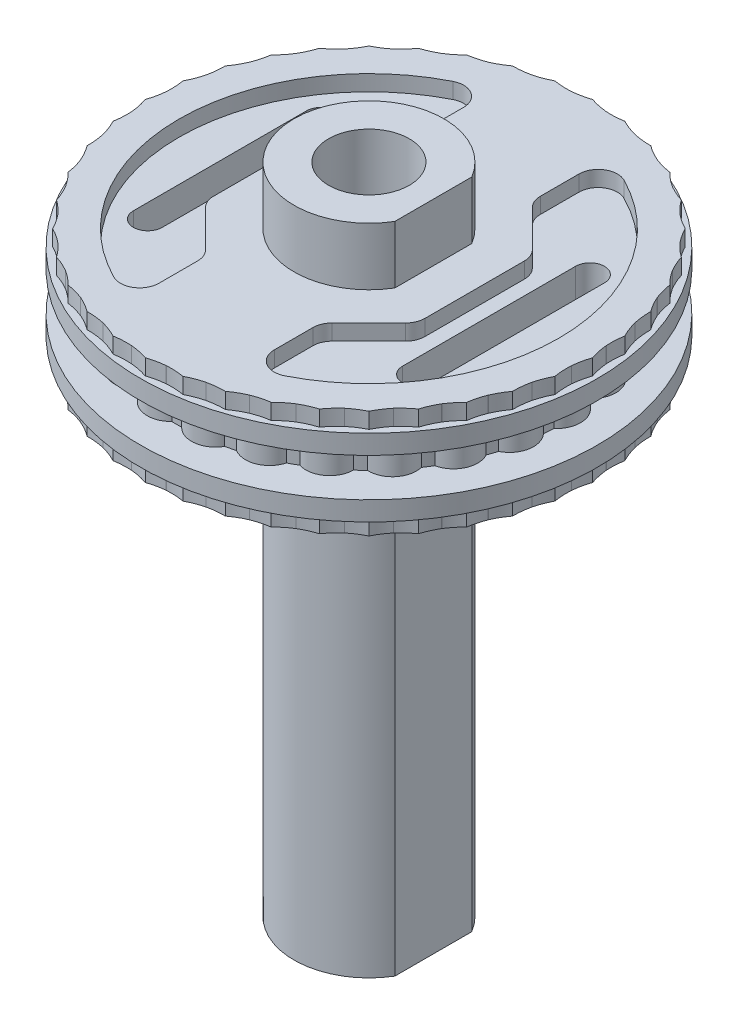
SolidWorks part; units mm, degrees
ref_plane "Front Plane" through (0, 0, 0) normal (0, 0, 1) x (1, 0, 0)
ref_plane "Top Plane" through (0, 0, 0) normal (0, 1, 0) x (1, 0, 0)
ref_plane "Right Plane" through (0, 0, 0) normal (1, 0, 0) x (0, 0, -1)
sketch "Sketch1" plane through (0, 0, 0) normal (1, 0, 0) x (0, 0, -1)
  line L0 (0, -0.599) -> (0, 0.599) construction
  line L1 (-5, -0.5) -> (0, -0.5)
  line L2 (-5, -0.5) -> (-5, 0.5)
  line L3 (-5, 0.5) -> (0, 0.5)
  line L4 (0, -0.5) -> (0, 0.5)
  line L5 (-5, -0.5) -> (0, 0.5) construction
  line L6 (-5, 0.5) -> (0, -0.5) construction
  point P0 (-2.5, 0)
  point P8 (0, 0)
  dimension "D2" = 5
  dimension "D3" = 1
revolve "Revolve1" add sketch "Sketch1" angle 360 about L0
sketch "Sketch2" plane through (0, 0.5, 0) normal (0, 1, 0) x (1, 0, 0)
  line L0 (0, 0) -> (0, 5.2249) construction
  arc A0 (-0.5, 4.9749) -> (0.5, 4.9749) centre (0, 4.5999) cw
  circle A1 centre (0, 0) radius 5 construction
  circle A4 centre (0, 0) radius 5
  arc A5 (0.5, 4.9749) -> (-0.5, 4.9749) centre (0, 0) ccw
  dimension "D1" = 0
  dimension "D2" = 1
  dimension "D3" = 0.25
extrude "Boss-Extrude1" add sketch "Sketch2" against normal up to surface (1 mm away) from surface up to face at (0, -0.5, -5) starting at face at (0, 0.5, -5)
pattern_circular "CirPattern1" count 25 over 360 about axis through (0, 0.5, 0) along (0, -1, 0) of "Boss-Extrude1"
sketch "Sketch3" plane through (0, 0, 0) normal (1, 0, 0) x (0, 0, -1)
  line L0 (0, 0) -> (0, 0.5) construction
  line L1 (0, 0.5) -> (-5.9387, 0.5)
  line L3 (-5.7387, 1) -> (-5.9387, 1)
  line L4 (-5.9387, 0.5) -> (-5.9387, 1)
  line L6 (0, 0.5) -> (0, 1.4)
  line L7 (0, 1.4) -> (-5.7387, 1.4)
  line L8 (-5.7387, 1) -> (-5.7387, 1.4)
  line L9 (0.8114, 0.5) -> (-0.1866, 0.5) construction
  line L10 (-5.1887, 0.5) -> (-5.1887, -0.5) construction
  dimension "D1" = 0.5
  dimension "D2" = 0.4
  dimension "D3" = 0.75
  dimension "D4" = 0.2
revolve "Revolve2" add sketch "Sketch3" angle 360 about L0
sketch "Sketch4" plane through (0, 1.4, 0) normal (0, 1, 0) x (1, 0, 0)
  line L0 (0, 0) -> (0, 5.8168) construction
  arc A0 (-0.5, 5.7168) -> (0, 5.8168) centre (-0.639, 7.712) ccw
  arc A1 (0, 5.8168) -> (0.5, 5.7168) centre (0.639, 7.712) ccw
  circle A3 centre (0, 0) radius 5.7387 construction
  circle A4 centre (0, 0) radius 5.7387
  arc A5 (0.5, 5.7168) -> (-0.5, 5.7168) centre (0, 0) ccw
  circle M2 centre (0, 0) radius 5.7387
  dimension "D4" = 2
  dimension "D2" = 0.1
  dimension "D3" = 1
  dimension "D1" = 0
extrude "Boss-Extrude2" add sketch "Sketch4" against normal up to surface (0.4 mm away) contours L0 A1 M2 | A5 L0 A0 region at (-0.117, 1.4, -5.7602) region at (0.117, 1.4, -5.7602) up to face at (0, 1, -5.9387)
pattern_circular "CirPattern2" count 40 over 360 about axis through (0, 1.4, 0) along (0, -1, 0) of "Boss-Extrude2"
mirror "Mirror2" about plane through (0, 0, 0) normal (0, 1, 0) of "Revolve2", "Boss-Extrude2", "CirPattern2"
sketch "Sketch16" plane through (0, 1.4, 0) normal (0, 1, 0) x (1, 0, 0)
  line L80 (-1.3373, 5.5807) -> (-1.3421, 5.5795)
  line L81 (-2.1938, 5.3028) -> (-2.1984, 5.3009)
  line L82 (-2.9963, 4.8943) -> (-3.0006, 4.8917)
  line L83 (-3.7251, 4.3653) -> (-3.7289, 4.3621)
  line L84 (-4.3621, 3.7289) -> (-4.3653, 3.7251)
  line L85 (-4.8917, 3.0006) -> (-4.8943, 2.9963)
  line L86 (-5.3009, 2.1984) -> (-5.3028, 2.1938)
  line L87 (-5.5795, 1.3421) -> (-5.5807, 1.3373)
  line L88 (-5.7208, 0.4527) -> (-5.7212, 0.4478)
  line L89 (-5.7212, -0.4478) -> (-5.7208, -0.4527)
  line L90 (-5.5807, -1.3373) -> (-5.5795, -1.3421)
  line L91 (-5.3028, -2.1938) -> (-5.3009, -2.1984)
  line L92 (-4.8943, -2.9963) -> (-4.8917, -3.0006)
  line L93 (-4.3653, -3.7251) -> (-4.3621, -3.7289)
  line L94 (-3.7289, -4.3621) -> (-3.7251, -4.3653)
  line L95 (-3.0006, -4.8917) -> (-2.9963, -4.8943)
  line L96 (-2.1984, -5.3009) -> (-2.1938, -5.3028)
  line L97 (-1.3421, -5.5795) -> (-1.3373, -5.5807)
  line L98 (-0.4527, -5.7208) -> (-0.4478, -5.7212)
  line L99 (0.4478, -5.7212) -> (0.4527, -5.7208)
  line L100 (1.3373, -5.5807) -> (1.3421, -5.5795)
  line L101 (2.1938, -5.3028) -> (2.1984, -5.3009)
  line L102 (2.9963, -4.8943) -> (3.0006, -4.8917)
  line L103 (3.7251, -4.3653) -> (3.7289, -4.3621)
  line L104 (4.3621, -3.7289) -> (4.3653, -3.7251)
  line L105 (4.8917, -3.0006) -> (4.8943, -2.9963)
  line L106 (5.3009, -2.1984) -> (5.3028, -2.1938)
  line L107 (5.5795, -1.3421) -> (5.5807, -1.3373)
  line L108 (5.7208, -0.4527) -> (5.7212, -0.4478)
  line L109 (5.7212, 0.4478) -> (5.7208, 0.4527)
  line L110 (5.5807, 1.3373) -> (5.5795, 1.3421)
  line L111 (5.3028, 2.1938) -> (5.3009, 2.1984)
  line L112 (4.8943, 2.9963) -> (4.8917, 3.0006)
  line L113 (4.3653, 3.7251) -> (4.3621, 3.7289)
  line L114 (3.7289, 4.3621) -> (3.7251, 4.3653)
  line L115 (3.0006, 4.8917) -> (2.9963, 4.8943)
  line L116 (2.1984, 5.3009) -> (2.1938, 5.3028)
  line L117 (1.3421, 5.5795) -> (1.3373, 5.5807)
  line L118 (0.4527, 5.7208) -> (0.4478, 5.7212)
  line L119 (-0.4478, 5.7212) -> (-0.4527, 5.7208)
  line L120 (-1.3373, 5.5807) -> (-1.3421, 5.5795)
  line L121 (-2.1938, 5.3028) -> (-2.1984, 5.3009)
  line L122 (-2.9963, 4.8943) -> (-3.0006, 4.8917)
  line L123 (-3.7251, 4.3653) -> (-3.7289, 4.3621)
  line L124 (-4.3621, 3.7289) -> (-4.3653, 3.7251)
  line L125 (-4.8917, 3.0006) -> (-4.8943, 2.9963)
  line L126 (-5.3009, 2.1984) -> (-5.3028, 2.1938)
  line L127 (-5.5795, 1.3421) -> (-5.5807, 1.3373)
  line L128 (-5.7208, 0.4527) -> (-5.7212, 0.4478)
  line L129 (-5.7212, -0.4478) -> (-5.7208, -0.4527)
  line L130 (-5.5807, -1.3373) -> (-5.5795, -1.3421)
  line L131 (-5.3028, -2.1938) -> (-5.3009, -2.1984)
  line L132 (-4.8943, -2.9963) -> (-4.8917, -3.0006)
  line L133 (-4.3653, -3.7251) -> (-4.3621, -3.7289)
  line L134 (-3.7289, -4.3621) -> (-3.7251, -4.3653)
  line L135 (-3.0006, -4.8917) -> (-2.9963, -4.8943)
  line L136 (-2.1984, -5.3009) -> (-2.1938, -5.3028)
  line L137 (-1.3421, -5.5795) -> (-1.3373, -5.5807)
  line L138 (-0.4527, -5.7208) -> (-0.4478, -5.7212)
  line L139 (0.4478, -5.7212) -> (0.4527, -5.7208)
  line L140 (1.3373, -5.5807) -> (1.3421, -5.5795)
  line L141 (2.1938, -5.3028) -> (2.1984, -5.3009)
  line L142 (2.9963, -4.8943) -> (3.0006, -4.8917)
  line L143 (3.7251, -4.3653) -> (3.7289, -4.3621)
  line L144 (4.3621, -3.7289) -> (4.3653, -3.7251)
  line L145 (4.8917, -3.0006) -> (4.8943, -2.9963)
  line L146 (5.3009, -2.1984) -> (5.3028, -2.1938)
  line L147 (5.5795, -1.3421) -> (5.5807, -1.3373)
  line L148 (5.7208, -0.4527) -> (5.7212, -0.4478)
  line L149 (5.7212, 0.4478) -> (5.7208, 0.4527)
  line L150 (5.5807, 1.3373) -> (5.5795, 1.3421)
  line L151 (5.3028, 2.1938) -> (5.3009, 2.1984)
  line L152 (4.8943, 2.9963) -> (4.8917, 3.0006)
  line L153 (4.3653, 3.7251) -> (4.3621, 3.7289)
  line L154 (3.7289, 4.3621) -> (3.7251, 4.3653)
  line L155 (3.0006, 4.8917) -> (2.9963, 4.8943)
  line L156 (2.1984, 5.3009) -> (2.1938, 5.3028)
  line L157 (1.3421, 5.5795) -> (1.3373, 5.5807)
  line L158 (0.4527, 5.7208) -> (0.4478, 5.7212)
  line L159 (-0.4478, 5.7212) -> (-0.4527, 5.7208)
  arc A160 (-1.7975, 5.5321) -> (-1.3421, 5.5795) centre (-1.7754, 7.532) ccw
  arc A161 (-2.1938, 5.3028) -> (-1.7975, 5.5321) centre (-2.9909, 7.1371) ccw
  arc A162 (-2.6408, 5.1828) -> (-2.1984, 5.3009) centre (-2.9318, 7.1616) ccw
  arc A163 (-2.9963, 4.8943) -> (-2.6408, 5.1828) centre (-4.0706, 6.5813) ccw
  arc A164 (-3.4191, 4.7059) -> (-3.0006, 4.8917) centre (-4.016, 6.6148) ccw
  arc A165 (-3.7251, 4.3653) -> (-3.4191, 4.7059) centre (-5.05, 5.8635) ccw
  arc A166 (-4.1131, 4.1131) -> (-3.7289, 4.3621) centre (-5.0013, 5.9051) ccw
  arc A167 (-4.3621, 3.7289) -> (-4.1131, 4.1131) centre (-5.9051, 5.0013) ccw
  arc A168 (-4.7059, 3.4191) -> (-4.3653, 3.7251) centre (-5.8635, 5.05) ccw
  arc A169 (-4.8917, 3.0006) -> (-4.7059, 3.4191) centre (-6.6148, 4.016) ccw
  arc A170 (-5.1828, 2.6408) -> (-4.8943, 2.9963) centre (-6.5813, 4.0706) ccw
  arc A171 (-5.3009, 2.1984) -> (-5.1828, 2.6408) centre (-7.1616, 2.9318) ccw
  arc A172 (-5.5321, 1.7975) -> (-5.3028, 2.1938) centre (-7.1371, 2.9909) ccw
  arc A173 (-5.5795, 1.3421) -> (-5.5321, 1.7975) centre (-7.532, 1.7754) ccw
  arc A174 (-5.7452, 0.91) -> (-5.5807, 1.3373) centre (-7.5171, 1.8376) ccw
  arc A175 (-5.7208, 0.4527) -> (-5.7452, 0.91) centre (-7.717, 0.5753) ccw
  arc A176 (-5.8168, 0) -> (-5.7212, 0.4478) centre (-7.712, 0.639) ccw
  arc A177 (-5.7212, -0.4478) -> (-5.8168, 0) centre (-7.712, -0.639) ccw
  arc A178 (-5.7452, -0.91) -> (-5.7208, -0.4527) centre (-7.717, -0.5753) ccw
  arc A179 (-5.5807, -1.3373) -> (-5.7452, -0.91) centre (-7.5171, -1.8376) ccw
  arc A180 (-5.5321, -1.7975) -> (-5.5795, -1.3421) centre (-7.532, -1.7754) ccw
  arc A181 (-5.3028, -2.1938) -> (-5.5321, -1.7975) centre (-7.1371, -2.9909) ccw
  arc A182 (-5.1828, -2.6408) -> (-5.3009, -2.1984) centre (-7.1616, -2.9318) ccw
  arc A183 (-4.8943, -2.9963) -> (-5.1828, -2.6408) centre (-6.5813, -4.0706) ccw
  arc A184 (-4.7059, -3.4191) -> (-4.8917, -3.0006) centre (-6.6148, -4.016) ccw
  arc A185 (-4.3653, -3.7251) -> (-4.7059, -3.4191) centre (-5.8635, -5.05) ccw
  arc A186 (-4.1131, -4.1131) -> (-4.3621, -3.7289) centre (-5.9051, -5.0013) ccw
  arc A187 (-3.7289, -4.3621) -> (-4.1131, -4.1131) centre (-5.0013, -5.9051) ccw
  arc A188 (-3.4191, -4.7059) -> (-3.7251, -4.3653) centre (-5.05, -5.8635) ccw
  arc A189 (-3.0006, -4.8917) -> (-3.4191, -4.7059) centre (-4.016, -6.6148) ccw
  arc A190 (-2.6408, -5.1828) -> (-2.9963, -4.8943) centre (-4.0706, -6.5813) ccw
  arc A191 (-2.1984, -5.3009) -> (-2.6408, -5.1828) centre (-2.9318, -7.1616) ccw
  arc A192 (-1.7975, -5.5321) -> (-2.1938, -5.3028) centre (-2.9909, -7.1371) ccw
  arc A193 (-1.3421, -5.5795) -> (-1.7975, -5.5321) centre (-1.7754, -7.532) ccw
  arc A194 (-0.91, -5.7452) -> (-1.3373, -5.5807) centre (-1.8376, -7.5171) ccw
  arc A195 (-0.4527, -5.7208) -> (-0.91, -5.7452) centre (-0.5753, -7.717) ccw
  arc A196 (0, -5.8168) -> (-0.4478, -5.7212) centre (-0.639, -7.712) ccw
  arc A197 (0.4478, -5.7212) -> (0, -5.8168) centre (0.639, -7.712) ccw
  arc A198 (0.91, -5.7452) -> (0.4527, -5.7208) centre (0.5753, -7.717) ccw
  arc A199 (1.3373, -5.5807) -> (0.91, -5.7452) centre (1.8376, -7.5171) ccw
  arc A200 (1.7975, -5.5321) -> (1.3421, -5.5795) centre (1.7754, -7.532) ccw
  arc A201 (2.1938, -5.3028) -> (1.7975, -5.5321) centre (2.9909, -7.1371) ccw
  arc A202 (2.6408, -5.1828) -> (2.1984, -5.3009) centre (2.9318, -7.1616) ccw
  arc A203 (2.9963, -4.8943) -> (2.6408, -5.1828) centre (4.0706, -6.5813) ccw
  arc A204 (3.4191, -4.7059) -> (3.0006, -4.8917) centre (4.016, -6.6148) ccw
  arc A205 (3.7251, -4.3653) -> (3.4191, -4.7059) centre (5.05, -5.8635) ccw
  arc A206 (4.1131, -4.1131) -> (3.7289, -4.3621) centre (5.0013, -5.9051) ccw
  arc A207 (4.3621, -3.7289) -> (4.1131, -4.1131) centre (5.9051, -5.0013) ccw
  arc A208 (4.7059, -3.4191) -> (4.3653, -3.7251) centre (5.8635, -5.05) ccw
  arc A209 (4.8917, -3.0006) -> (4.7059, -3.4191) centre (6.6148, -4.016) ccw
  arc A210 (5.1828, -2.6408) -> (4.8943, -2.9963) centre (6.5813, -4.0706) ccw
  arc A211 (5.3009, -2.1984) -> (5.1828, -2.6408) centre (7.1616, -2.9318) ccw
  arc A212 (5.5321, -1.7975) -> (5.3028, -2.1938) centre (7.1371, -2.9909) ccw
  arc A213 (5.5795, -1.3421) -> (5.5321, -1.7975) centre (7.532, -1.7754) ccw
  arc A214 (5.7452, -0.91) -> (5.5807, -1.3373) centre (7.5171, -1.8376) ccw
  arc A215 (5.7208, -0.4527) -> (5.7452, -0.91) centre (7.717, -0.5753) ccw
  arc A216 (5.8168, 0) -> (5.7212, -0.4478) centre (7.712, -0.639) ccw
  arc A217 (5.7212, 0.4478) -> (5.8168, 0) centre (7.712, 0.639) ccw
  arc A218 (5.7452, 0.91) -> (5.7208, 0.4527) centre (7.717, 0.5753) ccw
  arc A219 (5.5807, 1.3373) -> (5.7452, 0.91) centre (7.5171, 1.8376) ccw
  arc A220 (5.5321, 1.7975) -> (5.5795, 1.3421) centre (7.532, 1.7754) ccw
  arc A221 (5.3028, 2.1938) -> (5.5321, 1.7975) centre (7.1371, 2.9909) ccw
  arc A222 (5.1828, 2.6408) -> (5.3009, 2.1984) centre (7.1616, 2.9318) ccw
  arc A223 (4.8943, 2.9963) -> (5.1828, 2.6408) centre (6.5813, 4.0706) ccw
  arc A224 (4.7059, 3.4191) -> (4.8917, 3.0006) centre (6.6148, 4.016) ccw
  arc A225 (4.3653, 3.7251) -> (4.7059, 3.4191) centre (5.8635, 5.05) ccw
  arc A226 (4.1131, 4.1131) -> (4.3621, 3.7289) centre (5.9051, 5.0013) ccw
  arc A227 (3.7289, 4.3621) -> (4.1131, 4.1131) centre (5.0013, 5.9051) ccw
  arc A228 (3.4191, 4.7059) -> (3.7251, 4.3653) centre (5.05, 5.8635) ccw
  arc A229 (3.0006, 4.8917) -> (3.4191, 4.7059) centre (4.016, 6.6148) ccw
  arc A230 (2.6408, 5.1828) -> (2.9963, 4.8943) centre (4.0706, 6.5813) ccw
  arc A231 (2.1984, 5.3009) -> (2.6408, 5.1828) centre (2.9318, 7.1616) ccw
  arc A232 (1.7975, 5.5321) -> (2.1938, 5.3028) centre (2.9909, 7.1371) ccw
  arc A233 (1.3421, 5.5795) -> (1.7975, 5.5321) centre (1.7754, 7.532) ccw
  arc A234 (0.91, 5.7452) -> (1.3373, 5.5807) centre (1.8376, 7.5171) ccw
  arc A235 (0.4527, 5.7208) -> (0.91, 5.7452) centre (0.5753, 7.717) ccw
  arc A236 (0, 5.8168) -> (0.4478, 5.7212) centre (0.639, 7.712) ccw
  arc A237 (-0.4478, 5.7212) -> (0, 5.8168) centre (-0.639, 7.712) ccw
  arc A238 (-0.91, 5.7452) -> (-0.4527, 5.7208) centre (-0.5753, 7.717) ccw
  arc A239 (-1.3373, 5.5807) -> (-0.91, 5.7452) centre (-1.8376, 7.5171) ccw
  arc A240 (-1.7975, 5.5321) -> (-1.3421, 5.5795) centre (-1.7754, 7.532) ccw
  arc A241 (-2.1938, 5.3028) -> (-1.7975, 5.5321) centre (-2.9909, 7.1371) ccw
  arc A242 (-2.6408, 5.1828) -> (-2.1984, 5.3009) centre (-2.9318, 7.1616) ccw
  arc A243 (-2.9963, 4.8943) -> (-2.6408, 5.1828) centre (-4.0706, 6.5813) ccw
  arc A244 (-3.4191, 4.7059) -> (-3.0006, 4.8917) centre (-4.016, 6.6148) ccw
  arc A245 (-3.7251, 4.3653) -> (-3.4191, 4.7059) centre (-5.05, 5.8635) ccw
  arc A246 (-4.1131, 4.1131) -> (-3.7289, 4.3621) centre (-5.0013, 5.9051) ccw
  arc A247 (-4.3621, 3.7289) -> (-4.1131, 4.1131) centre (-5.9051, 5.0013) ccw
  arc A248 (-4.7059, 3.4191) -> (-4.3653, 3.7251) centre (-5.8635, 5.05) ccw
  arc A249 (-4.8917, 3.0006) -> (-4.7059, 3.4191) centre (-6.6148, 4.016) ccw
  arc A250 (-5.1828, 2.6408) -> (-4.8943, 2.9963) centre (-6.5813, 4.0706) ccw
  arc A251 (-5.3009, 2.1984) -> (-5.1828, 2.6408) centre (-7.1616, 2.9318) ccw
  arc A252 (-5.5321, 1.7975) -> (-5.3028, 2.1938) centre (-7.1371, 2.9909) ccw
  arc A253 (-5.5795, 1.3421) -> (-5.5321, 1.7975) centre (-7.532, 1.7754) ccw
  arc A254 (-5.7452, 0.91) -> (-5.5807, 1.3373) centre (-7.5171, 1.8376) ccw
  arc A255 (-5.7208, 0.4527) -> (-5.7452, 0.91) centre (-7.717, 0.5753) ccw
  arc A256 (-5.8168, 0) -> (-5.7212, 0.4478) centre (-7.712, 0.639) ccw
  arc A257 (-5.7212, -0.4478) -> (-5.8168, 0) centre (-7.712, -0.639) ccw
  arc A258 (-5.7452, -0.91) -> (-5.7208, -0.4527) centre (-7.717, -0.5753) ccw
  arc A259 (-5.5807, -1.3373) -> (-5.7452, -0.91) centre (-7.5171, -1.8376) ccw
  arc A260 (-5.5321, -1.7975) -> (-5.5795, -1.3421) centre (-7.532, -1.7754) ccw
  arc A261 (-5.3028, -2.1938) -> (-5.5321, -1.7975) centre (-7.1371, -2.9909) ccw
  arc A262 (-5.1828, -2.6408) -> (-5.3009, -2.1984) centre (-7.1616, -2.9318) ccw
  arc A263 (-4.8943, -2.9963) -> (-5.1828, -2.6408) centre (-6.5813, -4.0706) ccw
  arc A264 (-4.7059, -3.4191) -> (-4.8917, -3.0006) centre (-6.6148, -4.016) ccw
  arc A265 (-4.3653, -3.7251) -> (-4.7059, -3.4191) centre (-5.8635, -5.05) ccw
  arc A266 (-4.1131, -4.1131) -> (-4.3621, -3.7289) centre (-5.9051, -5.0013) ccw
  arc A267 (-3.7289, -4.3621) -> (-4.1131, -4.1131) centre (-5.0013, -5.9051) ccw
  arc A268 (-3.4191, -4.7059) -> (-3.7251, -4.3653) centre (-5.05, -5.8635) ccw
  arc A269 (-3.0006, -4.8917) -> (-3.4191, -4.7059) centre (-4.016, -6.6148) ccw
  arc A270 (-2.6408, -5.1828) -> (-2.9963, -4.8943) centre (-4.0706, -6.5813) ccw
  arc A271 (-2.1984, -5.3009) -> (-2.6408, -5.1828) centre (-2.9318, -7.1616) ccw
  arc A272 (-1.7975, -5.5321) -> (-2.1938, -5.3028) centre (-2.9909, -7.1371) ccw
  arc A273 (-1.3421, -5.5795) -> (-1.7975, -5.5321) centre (-1.7754, -7.532) ccw
  arc A274 (-0.91, -5.7452) -> (-1.3373, -5.5807) centre (-1.8376, -7.5171) ccw
  arc A275 (-0.4527, -5.7208) -> (-0.91, -5.7452) centre (-0.5753, -7.717) ccw
  arc A276 (0, -5.8168) -> (-0.4478, -5.7212) centre (-0.639, -7.712) ccw
  arc A277 (0.4478, -5.7212) -> (0, -5.8168) centre (0.639, -7.712) ccw
  arc A278 (0.91, -5.7452) -> (0.4527, -5.7208) centre (0.5753, -7.717) ccw
  arc A279 (1.3373, -5.5807) -> (0.91, -5.7452) centre (1.8376, -7.5171) ccw
  arc A280 (1.7975, -5.5321) -> (1.3421, -5.5795) centre (1.7754, -7.532) ccw
  arc A281 (2.1938, -5.3028) -> (1.7975, -5.5321) centre (2.9909, -7.1371) ccw
  arc A282 (2.6408, -5.1828) -> (2.1984, -5.3009) centre (2.9318, -7.1616) ccw
  arc A283 (2.9963, -4.8943) -> (2.6408, -5.1828) centre (4.0706, -6.5813) ccw
  arc A284 (3.4191, -4.7059) -> (3.0006, -4.8917) centre (4.016, -6.6148) ccw
  arc A285 (3.7251, -4.3653) -> (3.4191, -4.7059) centre (5.05, -5.8635) ccw
  arc A286 (4.1131, -4.1131) -> (3.7289, -4.3621) centre (5.0013, -5.9051) ccw
  arc A287 (4.3621, -3.7289) -> (4.1131, -4.1131) centre (5.9051, -5.0013) ccw
  arc A288 (4.7059, -3.4191) -> (4.3653, -3.7251) centre (5.8635, -5.05) ccw
  arc A289 (4.8917, -3.0006) -> (4.7059, -3.4191) centre (6.6148, -4.016) ccw
  arc A290 (5.1828, -2.6408) -> (4.8943, -2.9963) centre (6.5813, -4.0706) ccw
  arc A291 (5.3009, -2.1984) -> (5.1828, -2.6408) centre (7.1616, -2.9318) ccw
  arc A292 (5.5321, -1.7975) -> (5.3028, -2.1938) centre (7.1371, -2.9909) ccw
  arc A293 (5.5795, -1.3421) -> (5.5321, -1.7975) centre (7.532, -1.7754) ccw
  arc A294 (5.7452, -0.91) -> (5.5807, -1.3373) centre (7.5171, -1.8376) ccw
  arc A295 (5.7208, -0.4527) -> (5.7452, -0.91) centre (7.717, -0.5753) ccw
  arc A296 (5.8168, 0) -> (5.7212, -0.4478) centre (7.712, -0.639) ccw
  arc A297 (5.7212, 0.4478) -> (5.8168, 0) centre (7.712, 0.639) ccw
  arc A298 (5.7452, 0.91) -> (5.7208, 0.4527) centre (7.717, 0.5753) ccw
  arc A299 (5.5807, 1.3373) -> (5.7452, 0.91) centre (7.5171, 1.8376) ccw
  arc A300 (5.5321, 1.7975) -> (5.5795, 1.3421) centre (7.532, 1.7754) ccw
  arc A301 (5.3028, 2.1938) -> (5.5321, 1.7975) centre (7.1371, 2.9909) ccw
  arc A302 (5.1828, 2.6408) -> (5.3009, 2.1984) centre (7.1616, 2.9318) ccw
  arc A303 (4.8943, 2.9963) -> (5.1828, 2.6408) centre (6.5813, 4.0706) ccw
  arc A304 (4.7059, 3.4191) -> (4.8917, 3.0006) centre (6.6148, 4.016) ccw
  arc A305 (4.3653, 3.7251) -> (4.7059, 3.4191) centre (5.8635, 5.05) ccw
  arc A306 (4.1131, 4.1131) -> (4.3621, 3.7289) centre (5.9051, 5.0013) ccw
  arc A307 (3.7289, 4.3621) -> (4.1131, 4.1131) centre (5.0013, 5.9051) ccw
  arc A308 (3.4191, 4.7059) -> (3.7251, 4.3653) centre (5.05, 5.8635) ccw
  arc A309 (3.0006, 4.8917) -> (3.4191, 4.7059) centre (4.016, 6.6148) ccw
  arc A310 (2.6408, 5.1828) -> (2.9963, 4.8943) centre (4.0706, 6.5813) ccw
  arc A311 (2.1984, 5.3009) -> (2.6408, 5.1828) centre (2.9318, 7.1616) ccw
  arc A312 (1.7975, 5.5321) -> (2.1938, 5.3028) centre (2.9909, 7.1371) ccw
  arc A313 (1.3421, 5.5795) -> (1.7975, 5.5321) centre (1.7754, 7.532) ccw
  arc A314 (0.91, 5.7452) -> (1.3373, 5.5807) centre (1.8376, 7.5171) ccw
  arc A315 (0.4527, 5.7208) -> (0.91, 5.7452) centre (0.5753, 7.717) ccw
  arc A316 (0, 5.8168) -> (0.4478, 5.7212) centre (0.639, 7.712) ccw
  arc A317 (-0.4478, 5.7212) -> (0, 5.8168) centre (-0.639, 7.712) ccw
  arc A318 (-0.91, 5.7452) -> (-0.4527, 5.7208) centre (-0.5753, 7.717) ccw
  arc A319 (-1.3373, 5.5807) -> (-0.91, 5.7452) centre (-1.8376, 7.5171) ccw
  dimension "D1" = 0
extrude "Boss-Extrude4" add sketch "Sketch16" along normal blind 0.01
sketch "Sketch5" plane through (0, 1.41, 0) normal (0, 1, 0) x (1, 0, 0)
  line L0 (1.6741, 1) -> (1.6741, -1)
  arc A0 (1.6741, 1) -> (1.6741, -1) centre (0, 0) ccw
  point P5 (1.6741, 0)
  dimension "D1" = 3.9
  dimension "D2" = 2
extrude "Boss-Extrude3" add sketch "Sketch5" against normal blind 17 from offset 1.5
sketch "Sketch7" plane through (0, 0, 0) normal (0, -1, 0) x (1, 0, 0)
  line L0 (-3.5, -2.25) -> (-3.5, 2.25) construction
  line L1 (-3.875, -2.25) -> (-3.875, 2.25)
  line L2 (-3.125, -2.25) -> (-3.125, 2.25)
  line L3 (0, 0) -> (0, 3.3928) construction
  line L4 (3.5, -2.25) -> (3.5, 2.25) construction
  line L5 (3.875, -2.25) -> (3.875, 2.25)
  line L6 (3.125, -2.25) -> (3.125, 2.25)
  arc A0 (-3.875, -2.25) -> (-3.125, -2.25) centre (-3.5, -2.25) ccw
  arc A1 (-3.125, 2.25) -> (-3.875, 2.25) centre (-3.5, 2.25) ccw
  arc A2 (3.875, -2.25) -> (3.125, -2.25) centre (3.5, -2.25) cw
  arc A3 (3.125, 2.25) -> (3.875, 2.25) centre (3.5, 2.25) cw
  point P2 (-3.5, 0)
  point P14 (3.5, 0)
  dimension "D1" = 3.5
  dimension "D2" = 0.75
  dimension "D3" = 4.5
extrude "Cut-Extrude2" cut sketch "Sketch7" against normal through all both and the other way through all
sketch "Sketch9" plane through (0, 1.41, 0) normal (0, 1, 0) x (1, 0, 0)
  line L0 (-1.5, 3.9625) -> (-1.5, 2.9571)
  line L1 (0, 0) -> (-1.5, 0) construction
  line L2 (-2.75, -1.2929) -> (-2.75, 1.2929)
  line L3 (-2.6036, 1.6464) -> (-1.6464, 2.6036)
  line L4 (-2.6036, -1.6464) -> (-1.6464, -2.6036)
  line L5 (-1.5, 0) -> (-2.75, 0) construction
  line L6 (-1.5, -2.9571) -> (-1.5, -3.9625)
  arc A0 (-1.5, -3.9625) -> (-2.2253, -4.4089) centre (-2, -3.9625) cw
  arc A1 (-1.5, 3.9625) -> (-2.2253, 4.4089) centre (-2, 3.9625) ccw
  circle A2 centre (0, 0) radius 4.9387
  arc A3 (-2.2253, 4.4089) -> (-2.2253, -4.4089) centre (0, 0) ccw
  arc A4 (-1.5, 2.9571) -> (-1.6464, 2.6036) centre (-2, 2.9571) cw
  arc A5 (-1.6464, -2.6036) -> (-1.5, -2.9571) centre (-2, -2.9571) cw
  arc A6 (-2.75, 1.2929) -> (-2.6036, 1.6464) centre (-2.25, 1.2929) cw
  arc A7 (-2.6036, -1.6464) -> (-2.75, -1.2929) centre (-2.25, -1.2929) cw
  point P18 (-1.5, 2.75)
  point P21 (-1.5, -2.75)
  point P24 (-2.75, 1.5)
  point P27 (-2.75, -1.5)
  dimension "D6" = 0.5
  dimension "D2" = 1.5
  dimension "D3" = 1.25
  dimension "D4" = 3
  dimension "D5" = 45
  dimension "D1" = 1
extrude "Cut-Extrude3" cut sketch "Sketch9" against normal up to surface (0.41 mm away) up to face at (0, 1, -5.9387)
mirror "Mirror3" about plane through (0, 0, 0) normal (1, 0, 0) of "Cut-Extrude3"
sketch "Sketch12" plane through (0, 2.91, 0) normal (0, 1, 0) x (1, 0, 0)
  circle A0 centre (0, 0) radius 5.9387 construction
  point P0 (0, 0)
hole_wizard "Ø2.0mm Dowel Hole1" positions "Sketch12" profile "Sketch11" hole size "Ø2.0" standard "ANSI Metric"
sketch "Sketch11" plane through (0, 2.91, 0) normal (1, 0, 0) x (0, 0, 1)
  line L0 (0, 0) -> (0, 8)
  line L1 (0, 8) -> (1.05, 7.3691)
  line L2 (1.05, 7.3691) -> (1.05, 0)
  line L5 (1.05, 0) -> (0, 0)
  line L10 (0, 8) -> (-1.05, 7.3691) construction
  line L11 (0, -6.35) -> (0, 107.95) construction
  dimension "Hole Dia." = 2.1
  dimension "Hole Depth" = 8
  dimension "Drill Angle" = 118
sketch "Sketch15" plane through (0, -14.09, 0) normal (0, -1, 0) x (-1, 0, 0)
  point P0 (0, 0)
hole_wizard "Ø2.0mm Dowel Hole2" positions "Sketch15" profile "Sketch14" hole size "Ø2.0" standard "ANSI Metric"
sketch "Sketch14" plane through (0, -14.09, 0) normal (1, 0, 0) x (0, 0, -1)
  line L0 (0, 0) -> (0, 8)
  line L1 (0, 8) -> (1.05, 7.3691)
  line L2 (1.05, 7.3691) -> (1.05, 0)
  line L5 (1.05, 0) -> (0, 0)
  line L10 (0, 8) -> (-1.05, 7.3691) construction
  line L11 (0, -6.35) -> (0, 107.95) construction
  dimension "Hole Dia." = 2.1
  dimension "Hole Depth" = 8
  dimension "Drill Angle" = 118
